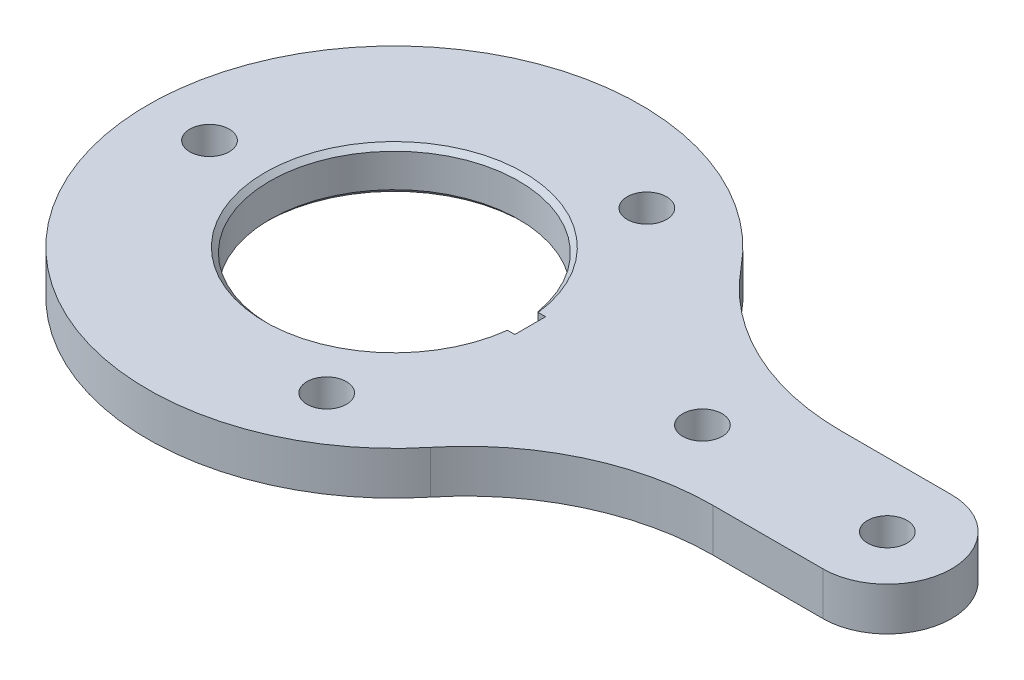
SolidWorks part; units mm, degrees
ref_plane "Front Plane" through (0, 0, 0) normal (0, 0, 1) x (1, 0, 0)
ref_plane "Top Plane" through (0, 0, 0) normal (0, 1, 0) x (1, 0, 0)
ref_plane "Right Plane" through (0, 0, 0) normal (1, 0, 0) x (0, 0, -1)
sketch "Sketch1" plane through (0, 0, 0) normal (0, 0, 1) x (1, 0, 0)
  line L1 (-35, 1.75) -> (35, 1.75)
  line L2 (-35, 1.75) -> (-35, -1.75)
  line L3 (-35, -1.75) -> (35, -1.75)
  line L4 (35, 1.75) -> (35, -1.75)
  line L5 (-35, 1.75) -> (35, -1.75) construction
  line L6 (-35, -1.75) -> (35, 1.75) construction
  point P0 (0, 0)
  dimension "D1" = 3.5
  dimension "D2" = 70
extrude "Boss-Extrude1" add sketch "Sketch1" along normal mid plane 50
sketch "Sketch2" plane through (0, 1.75, 0) normal (0, 1, 0) x (1, 0, 0)
  line L0 (-44.2539, 0) -> (44.2539, 0) construction
  line L1 (-14, 0) -> (-29.6753, 0) construction
  line L2 (-14, 0) -> (-6.5, 12.9904) construction
  line L3 (-14, 0) -> (-6.5, -12.9904) construction
  circle A0 centre (-14, 0) radius 10.1
  circle A2 centre (-29, 0) radius 1.6
  circle A3 centre (-6.5, 12.9904) radius 1.6
  circle A4 centre (-6.5, -12.9904) radius 1.6
  circle A5 centre (11, 0) radius 1.6
  circle A6 centre (26, 0) radius 1.6
  point P16 (0, 0)
  point P17 (0, 0)
  dimension "D1" = 20.2
  dimension "D2" = 120
  dimension "D8" = 3.2
  dimension "D9" = 3.2
  dimension "D10" = 3.2
  dimension "D11" = 3.2
  dimension "D12" = 3.2
  dimension "D3" = 120
  dimension "D4" = 14
  dimension "D5" = 15
  dimension "D6" = 15
  dimension "D7" = 15
  dimension "D13" = 15
  dimension "D14" = 25
extrude "Cut-Extrude1" cut sketch "Sketch2" against normal through all
sketch "Sketch4" plane through (0, 1.75, 0) normal (0, 1, 0) x (1, 0, 0)
  line L0 (-44.2539, 0) -> (44.2539, 0) construction
  line L1 (17.0547, -5.2147) -> (26, -5.2147)
  line L2 (17.0547, 5.2147) -> (26, 5.2147)
  arc A0 (1.525, 12.6085) -> (1.525, -12.6085) centre (-14, 0) ccw
  circle A1 centre (-14, 0) radius 10.1 construction
  arc A2 (1.525, -12.6085) -> (17.0547, -5.2147) centre (17.0547, -25.2207) cw
  arc A3 (26, -5.2147) -> (26, 5.2147) centre (26, 0) ccw
  circle A4 centre (26, 0) radius 1.6 construction
  arc A5 (1.525, 12.6085) -> (17.0547, 5.2147) centre (17.0547, 25.2207) ccw
  dimension "D1" = 20
extrude "Cut-Extrude2" cut sketch "Sketch4" against normal through all flip side to cut
sketch "Sketch5" plane through (0, 1.75, 0) normal (0, 1, 0) x (1, 0, 0)
  line L0 (-44.2539, 0) -> (44.2539, 0) construction
  line L1 (-2.9776, -1.25) -> (-3.9776, -1.25)
  line L2 (-2.9776, -1.25) -> (-2.9776, 1.25)
  line L3 (-2.9776, 1.25) -> (-3.9776, 1.25)
  line L4 (-3.9776, -1.25) -> (-3.9776, 1.25)
  line L5 (-2.9776, -1.25) -> (-3.9776, 1.25) construction
  line L6 (-2.9776, 1.25) -> (-3.9776, -1.25) construction
  circle A0 centre (-14, 0) radius 10.1 construction
  point P0 (-3.4776, 0)
  dimension "D1" = 1
  dimension "D2" = 2.5
extrude "Cut-Extrude3" cut sketch "Sketch5" against normal through all
chamfer "Chamfer1" distance 0.4 angle 45 4 edges at (-24.1, -1.75, 0) (-24.1, 1.75, 0) (-3.9776, 0, 1.25) (-3.9776, 0, -1.25)
